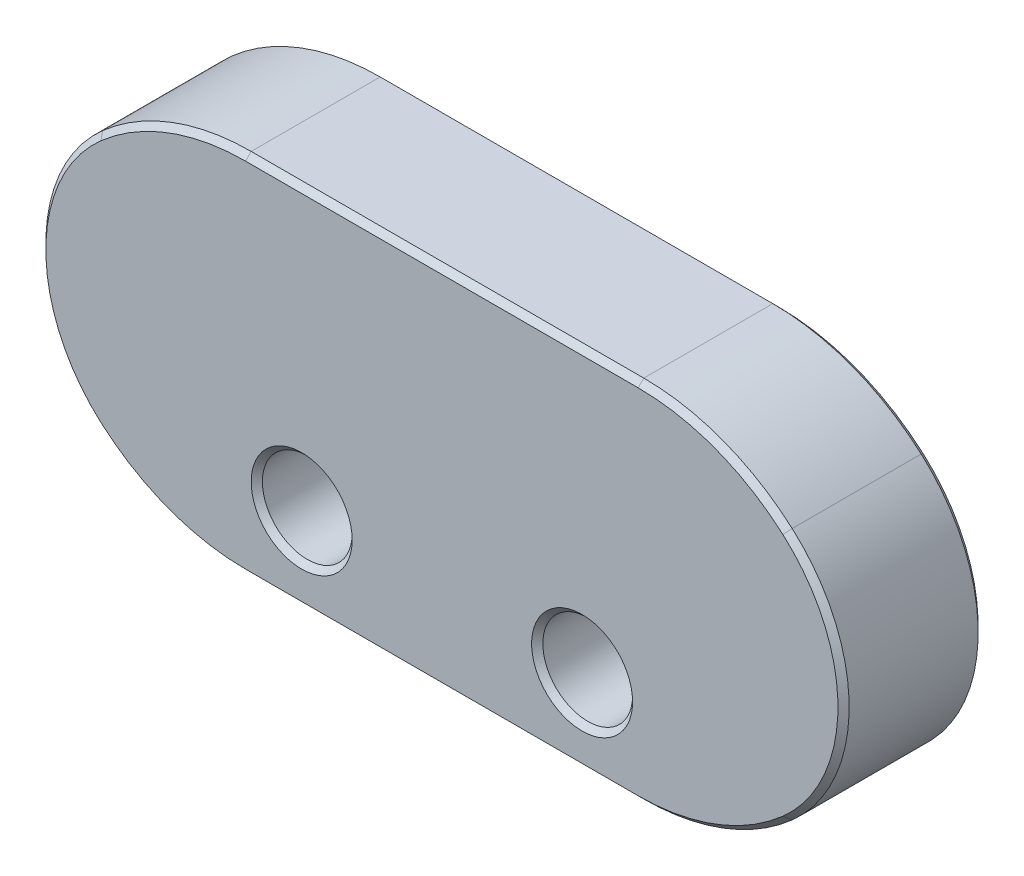
SolidWorks part; units mm, degrees
ref_plane "Front Plane" through (0, 0, 0) normal (0, 0, 1) x (1, 0, 0)
ref_plane "Top Plane" through (0, 0, 0) normal (0, 1, 0) x (1, 0, 0)
ref_plane "Right Plane" through (0, 0, 0) normal (1, 0, 0) x (0, 0, -1)
sketch "Sketch1" plane through (0, 0, 0) normal (0, 0, 1) x (1, 0, 0)
  line L1 (0, 0) -> (30, 0)
  line L2 (0, 0) -> (0, -13)
  line L3 (0, -13) -> (30, -13)
  line L4 (30, 0) -> (30, -13)
  dimension "D1" = 30
  dimension "D2" = 13
extrude "Boss-Extrude1" add sketch "Sketch1" along normal blind 5
sketch "Sketch2" plane through (0, 0, 0) normal (0, 0, -1) x (-1, 0, 0)
  line L0 (-30, 0) -> (0, 0) construction
  line L1 (-30, -13) -> (-30, 0) construction
  line L2 (0, 0) -> (0, -13) construction
  circle A0 centre (-20, -10) radius 1.6
  circle A1 centre (-10, -10) radius 1.6
  dimension "D5" = 3.2
  dimension "D6" = 3.2
  dimension "D1" = 10
  dimension "D2" = 10
  dimension "D3" = 10
  dimension "D4" = 10
extrude "Cut-Extrude1" cut sketch "Sketch2" against normal through all
fillet "Fillet1" radius 8 4 edges at (0, 0, 2.5) (0, -13, 2.5) (30, -13, 2.5) (30, 0, 2.5)
fillet "圆角2" radius 6 2 edges at (29.8581, -6.5, 2.5) (0.1419, -6.5, 2.5)
chamfer "倒角1" distance 0.2 angle 45 20 edges at (15, -13, 5) (5.1716, -12.4833, 5) (0.6771, -6.5, 5) (5.1716, -0.5167, 5) (15, 0, 5) (24.8284, -0.5167, 5) (29.3229, -6.5, 5) (24.8284, -12.4833, 5) (18.4, -10, 5) (8.4, -10, 5) (15, 0, 0) (5.1716, -0.5167, 0) (0.6771, -6.5, 0) (5.1716, -12.4833, 0) (15, -13, 0) (24.8284, -12.4833, 0) (29.3229, -6.5, 0) (24.8284, -0.5167, 0) (18.4, -10, 0) (8.4, -10, 0)
equation "\"D2@Sketch1\"=20-(20-6)/2"
